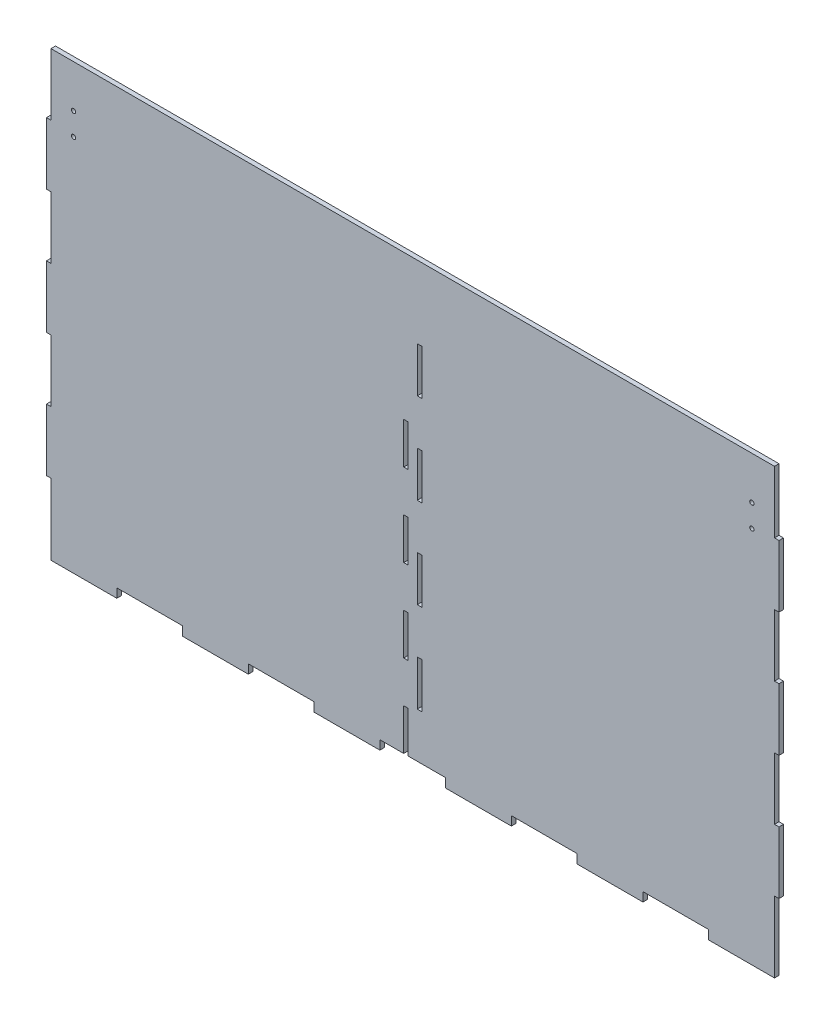
SolidWorks part; units mm, degrees
ref_plane "Front Plane" through (0, 0, 0) normal (0, 0, 1) x (1, 0, 0)
ref_plane "Top Plane" through (0, 0, 0) normal (0, 1, 0) x (1, 0, 0)
ref_plane "Right Plane" through (0, 0, 0) normal (1, 0, 0) x (0, 0, -1)
sketch "Sketch1" plane through (0, 0, 0) normal (0, 0, 1) x (1, 0, 0)
  line L0 (0, 0) -> (508, 0)
  line L1 (508, 0) -> (508, 304.8)
  line L2 (508, 304.8) -> (0, 304.8)
  line L3 (0, 304.8) -> (0, 0)
  line L4 (0, 0) -> (-3.175, 0)
  line L5 (-3.175, 0) -> (-3.175, 43.5429)
  line L6 (-3.175, 43.5429) -> (0, 43.5429)
  line L7 (0, 43.5429) -> (0, 0)
  line L8 (254, 304.8) -> (254, 0) construction
  line L9 (0, 43.5429) -> (-3.175, 43.5429)
  line L10 (-3.175, 43.5429) -> (-3.175, 87.0857)
  line L11 (-3.175, 87.0857) -> (0, 87.0857)
  line L12 (0, 87.0857) -> (0, 43.5429)
  line L13 (0, 87.0857) -> (-3.175, 87.0857)
  line L14 (-3.175, 87.0857) -> (-3.175, 130.6286)
  line L15 (-3.175, 130.6286) -> (0, 130.6286)
  line L16 (0, 130.6286) -> (0, 87.0857)
  line L17 (0, 130.6286) -> (-3.175, 130.6286)
  line L18 (-3.175, 130.6286) -> (-3.175, 174.1714)
  line L19 (-3.175, 174.1714) -> (0, 174.1714)
  line L20 (0, 174.1714) -> (0, 130.6286)
  line L21 (0, 174.1714) -> (-3.175, 174.1714)
  line L22 (-3.175, 174.1714) -> (-3.175, 217.7143)
  line L23 (-3.175, 217.7143) -> (0, 217.7143)
  line L24 (0, 217.7143) -> (0, 174.1714)
  line L25 (0, 217.7143) -> (-3.175, 217.7143)
  line L26 (-3.175, 217.7143) -> (-3.175, 261.2571)
  line L27 (-3.175, 261.2571) -> (0, 261.2571)
  line L28 (0, 261.2571) -> (0, 217.7143)
  line L29 (0, 261.2571) -> (-3.175, 261.2571)
  line L30 (-3.175, 261.2571) -> (-3.175, 304.8)
  line L31 (-3.175, 304.8) -> (0, 304.8)
  line L32 (0, 304.8) -> (0, 261.2571)
  line L33 (0, 0) -> (0, 43.5429) construction
  line L34 (508, 261.2571) -> (508, 217.7143)
  line L35 (511.175, 261.2571) -> (508, 261.2571)
  line L36 (511.175, 217.7143) -> (511.175, 261.2571)
  line L37 (508, 217.7143) -> (511.175, 217.7143)
  line L38 (508, 174.1714) -> (508, 130.6286)
  line L39 (511.175, 174.1714) -> (508, 174.1714)
  line L40 (511.175, 130.6286) -> (511.175, 174.1714)
  line L41 (508, 130.6286) -> (511.175, 130.6286)
  line L42 (508, 87.0857) -> (508, 43.5429)
  line L43 (511.175, 87.0857) -> (508, 87.0857)
  line L44 (511.175, 43.5429) -> (511.175, 87.0857)
  line L45 (508, 43.5429) -> (511.175, 43.5429)
  line L46 (0, 0) -> (0, -6.35)
  line L47 (0, -6.35) -> (46.1818, -6.35)
  line L48 (46.1818, -6.35) -> (46.1818, 0)
  line L49 (46.1818, 0) -> (0, 0)
  line L50 (46.1818, 0) -> (46.1818, -6.35)
  line L51 (46.1818, -6.35) -> (92.3636, -6.35)
  line L52 (92.3636, -6.35) -> (92.3636, 0)
  line L53 (92.3636, 0) -> (46.1818, 0)
  line L54 (92.3636, 0) -> (92.3636, -6.35)
  line L55 (92.3636, -6.35) -> (138.5455, -6.35)
  line L56 (138.5455, -6.35) -> (138.5455, 0)
  line L57 (138.5455, 0) -> (92.3636, 0)
  line L58 (138.5455, 0) -> (138.5455, -6.35)
  line L59 (138.5455, -6.35) -> (184.7273, -6.35)
  line L60 (184.7273, -6.35) -> (184.7273, 0)
  line L61 (184.7273, 0) -> (138.5455, 0)
  line L62 (184.7273, 0) -> (184.7273, -6.35)
  line L63 (184.7273, -6.35) -> (230.9091, -6.35)
  line L64 (230.9091, -6.35) -> (230.9091, 0)
  line L65 (230.9091, 0) -> (184.7273, 0)
  line L66 (230.9091, 0) -> (230.9091, -6.35)
  line L67 (230.9091, -6.35) -> (277.0909, -6.35)
  line L68 (277.0909, -6.35) -> (277.0909, 0)
  line L69 (277.0909, 0) -> (230.9091, 0)
  line L70 (277.0909, 0) -> (277.0909, -6.35)
  line L71 (277.0909, -6.35) -> (323.2727, -6.35)
  line L72 (323.2727, -6.35) -> (323.2727, 0)
  line L73 (323.2727, 0) -> (277.0909, 0)
  line L74 (323.2727, 0) -> (323.2727, -6.35)
  line L75 (323.2727, -6.35) -> (369.4545, -6.35)
  line L76 (369.4545, -6.35) -> (369.4545, 0)
  line L77 (369.4545, 0) -> (323.2727, 0)
  line L78 (369.4545, 0) -> (369.4545, -6.35)
  line L79 (369.4545, -6.35) -> (415.6364, -6.35)
  line L80 (415.6364, -6.35) -> (415.6364, 0)
  line L81 (415.6364, 0) -> (369.4545, 0)
  line L82 (415.6364, 0) -> (415.6364, -6.35)
  line L83 (415.6364, -6.35) -> (461.8182, -6.35)
  line L84 (461.8182, -6.35) -> (461.8182, 0)
  line L85 (461.8182, 0) -> (415.6364, 0)
  line L86 (461.8182, 0) -> (461.8182, -6.35)
  line L87 (461.8182, -6.35) -> (508, -6.35)
  line L88 (508, -6.35) -> (508, 0)
  line L89 (508, 0) -> (461.8182, 0)
  line L90 (0, 0) -> (46.1818, 0) construction
  dimension "D1" = 508
  dimension "D2" = 304.8
  dimension "D3" = 3.175
  dimension "D5" = 43.5429
  dimension "D6" = 43.5429
  dimension "D7" = 6.35
  dimension "D9" = 46.1818
  dimension "D10" = 46.1818
  dimension "D4" = 7
  dimension "D8" = 11
extrude "Boss-Extrude1" add sketch "Sketch1" along normal blind 3.175 contours L2 L3 L0 L1 | L47 L48 L0 L46 | L55 L56 L0 L52 | L63 L64 L0 L60 | L71 L72 L0 L68 | L79 L80 L0 L76 | L87 L88 L0 L84 | L1 L45 L44 L43 | L1 L41 L40 L39 | L1 L37 L36 L35 | L26 L27 L28 L25 | L18 L19 L20 L17 | L10 L11 L12 L9 region at (254, 152.4, 0) region at (23.0909, -3.175, 0) region at (115.4545, -3.175, 0) region at (207.8182, -3.175, 0) region at (300.1818, -3.175, 0) region at (392.5455, -3.175, 0) region at (509.5875, 239.4857, 0) region at (484.9091, -3.175, 0) region at (509.5875, 152.4, 0) region at (509.5875, 65.3143, 0)
sketch "Sketch2" plane through (0, 0, 3.175) normal (0, 0, 1) x (1, 0, 0)
  line L0 (254, 304.8) -> (254, 0) construction
  line L1 (508, 304.8) -> (0, 304.8) construction
  line L2 (230.9091, 0) -> (277.0909, 0) construction
  line L4 (-3.175, 217.7143) -> (-3.175, 261.2571) construction
  circle A0 centre (15.875, 274.8) radius 1.5
  circle A1 centre (15.875, 259.05) radius 1.5
  circle A2 centre (492.125, 259.05) radius 1.5
  circle A3 centre (492.125, 274.8) radius 1.5
  dimension "D1" = 3
  dimension "D2" = 3
  dimension "D3" = 15.75
  dimension "D4" = 19.05
  dimension "D5" = 30
extrude "Cut-Extrude1" cut sketch "Sketch2" against normal up to surface (3.175 mm away) up to face at (254, 87.3125, 0)
sketch "Sketch3" plane through (0, 0, 3.175) normal (0, 0, 1) x (1, 0, 0)
  line L0 (254, 304.8) -> (254, 0) construction
  line L1 (508, 304.8) -> (0, 304.8) construction
  line L2 (230.9091, 0) -> (277.0909, 0) construction
  line L3 (247.65, 0) -> (247.65, 29.0286)
  line L4 (247.65, 29.0286) -> (250.825, 29.0286)
  line L5 (250.825, 29.0286) -> (250.825, 0)
  line L6 (250.825, 0) -> (247.65, 0)
  line L7 (250.825, 29.0286) -> (247.65, 29.0286)
  line L8 (247.65, 29.0286) -> (247.65, 58.0571)
  line L9 (247.65, 58.0571) -> (250.825, 58.0571)
  line L10 (250.825, 58.0571) -> (250.825, 29.0286)
  line L11 (250.825, 58.0571) -> (247.65, 58.0571)
  line L12 (247.65, 58.0571) -> (247.65, 87.0857)
  line L13 (247.65, 87.0857) -> (250.825, 87.0857)
  line L14 (250.825, 87.0857) -> (250.825, 58.0571)
  line L15 (250.825, 87.0857) -> (247.65, 87.0857)
  line L16 (247.65, 87.0857) -> (247.65, 116.1143)
  line L17 (247.65, 116.1143) -> (250.825, 116.1143)
  line L18 (250.825, 116.1143) -> (250.825, 87.0857)
  line L19 (250.825, 116.1143) -> (247.65, 116.1143)
  line L20 (247.65, 116.1143) -> (247.65, 145.1429)
  line L21 (247.65, 145.1429) -> (250.825, 145.1429)
  line L22 (250.825, 145.1429) -> (250.825, 116.1143)
  line L23 (250.825, 145.1429) -> (247.65, 145.1429)
  line L24 (247.65, 145.1429) -> (247.65, 174.1714)
  line L25 (247.65, 174.1714) -> (250.825, 174.1714)
  line L26 (250.825, 174.1714) -> (250.825, 145.1429)
  line L27 (250.825, 174.1714) -> (247.65, 174.1714)
  line L28 (247.65, 174.1714) -> (247.65, 203.2)
  line L29 (247.65, 203.2) -> (250.825, 203.2)
  line L30 (250.825, 203.2) -> (250.825, 174.1714)
  line L31 (250.825, 0) -> (250.825, 29.0286) construction
  line L32 (257.175, 0) -> (260.35, 0)
  line L33 (260.35, 0) -> (260.35, 31.75)
  line L34 (260.35, 31.75) -> (257.175, 31.75)
  line L35 (257.175, 31.75) -> (257.175, 0)
  line L36 (257.175, 63.5) -> (257.175, 31.75)
  line L37 (257.175, 31.75) -> (260.35, 31.75)
  line L38 (260.35, 31.75) -> (260.35, 63.5)
  line L39 (260.35, 63.5) -> (257.175, 63.5)
  line L40 (257.175, 95.25) -> (257.175, 63.5)
  line L41 (257.175, 63.5) -> (260.35, 63.5)
  line L42 (260.35, 63.5) -> (260.35, 95.25)
  line L43 (260.35, 95.25) -> (257.175, 95.25)
  line L44 (257.175, 127) -> (257.175, 95.25)
  line L45 (257.175, 95.25) -> (260.35, 95.25)
  line L46 (260.35, 95.25) -> (260.35, 127)
  line L47 (260.35, 127) -> (257.175, 127)
  line L48 (257.175, 158.75) -> (257.175, 127)
  line L49 (257.175, 127) -> (260.35, 127)
  line L50 (260.35, 127) -> (260.35, 158.75)
  line L51 (260.35, 158.75) -> (257.175, 158.75)
  line L52 (257.175, 190.5) -> (257.175, 158.75)
  line L53 (257.175, 158.75) -> (260.35, 158.75)
  line L54 (260.35, 158.75) -> (260.35, 190.5)
  line L55 (260.35, 190.5) -> (257.175, 190.5)
  line L56 (257.175, 222.25) -> (257.175, 190.5)
  line L57 (257.175, 190.5) -> (260.35, 190.5)
  line L58 (260.35, 190.5) -> (260.35, 222.25)
  line L59 (260.35, 222.25) -> (257.175, 222.25)
  line L60 (257.175, 254) -> (257.175, 222.25)
  line L61 (257.175, 222.25) -> (260.35, 222.25)
  line L62 (260.35, 222.25) -> (260.35, 254)
  line L63 (260.35, 254) -> (257.175, 254)
  line L64 (257.175, 31.75) -> (257.175, 63.5) construction
  dimension "D4" = 7
  dimension "D1" = 3.175
  dimension "D2" = 3.175
  dimension "D3" = 29.0286
  dimension "D5" = 29.0286
  dimension "D6" = 3.175
  dimension "D7" = 3.175
  dimension "D8" = 31.75
  dimension "D10" = 31.75
  dimension "D9" = 8
extrude "Cut-Extrude2" cut sketch "Sketch3" against normal up to surface (3.175 mm away) contours L6 L5 L4 L3 | L14 L13 L12 L9 | L22 L21 L20 L17 | L30 L29 L28 L25 | L38 L39 L36 L34 | L46 L47 L44 L43 | L54 L55 L52 L51 | L62 L63 L60 L59 region at (249.2375, 14.5143, 3.175) region at (249.2375, 72.5714, 3.175) region at (249.2375, 130.6286, 3.175) region at (249.2375, 188.6857, 3.175) region at (258.7625, 47.625, 3.175) region at (258.7625, 111.125, 3.175) region at (258.7625, 174.625, 3.175) region at (258.7625, 238.125, 3.175) up to face at (493.625, 274.8, 0)
equation "\"Height\"= 12in"
equation "\"Depth\"= 7in"
equation "\"WallThickness\"= 0.125in"
equation "\"FloorThickness\"= 0.25in"
equation "\"Width\" = 30in"
equation "\"D7@Sketch1\"=\"FloorThickness\""
equation "\"D10@Sketch1\"=\"D1@Sketch1\"/\"D8@Sketch1\""
equation "\"D9@Sketch1\"=\"D10@Sketch1\""
equation "\"D1@Boss-Extrude1\"=\"WallThickness\""
equation "\"D1@Sketch3\"=\"WallThickness\""
equation "\"D2@Sketch3\"=\"FloorThickness\"/2"
equation "\"D5@Sketch3\"=\"D3@Sketch3\""
equation "\"D3@Sketch3\"=8in/\"D4@Sketch3\""
equation "\"D6@Sketch3\"=\"WallThickness\""
equation "\"D7@Sketch3\"=\"FloorThickness\"/2"
equation "\"D8@Sketch3\"=10in/\"D9@Sketch3\""
equation "\"D10@Sketch3\"=\"D8@Sketch3\""
